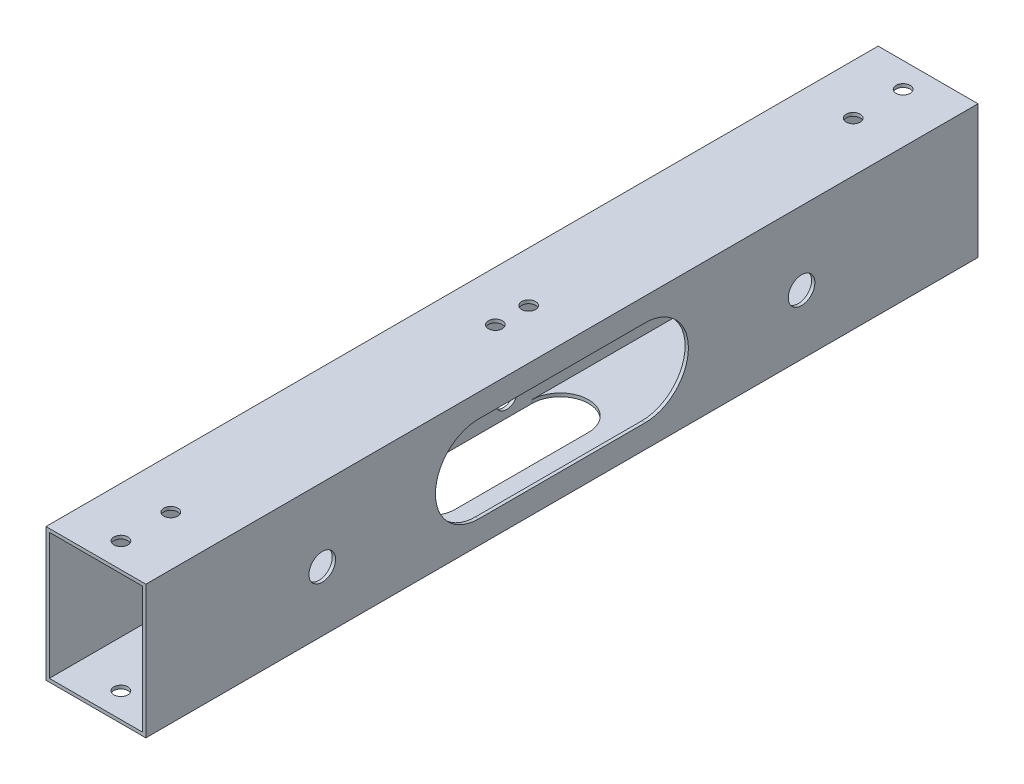
SolidWorks part; units mm, degrees
material "6061 合金"
ref_plane "前视基准面" through (0, 0, 0) normal (0, 0, 1) x (1, 0, 0)
ref_plane "上视基准面" through (0, 0, 0) normal (0, 1, 0) x (1, 0, 0)
ref_plane "右视基准面" through (0, 0, 0) normal (1, 0, 0) x (0, 0, -1)
other "Configuration Table"
sketch "草图1" plane through (0, 0, 0) normal (0, 0, 1) x (1, 0, 0)
  line L0 (15, -20) -> (15, 20)
  line L1 (15, 20) -> (-15, 20)
  line L2 (-15, 20) -> (-15, -20)
  line L3 (-15, -20) -> (15, -20)
  line L4 (14, 19) -> (-14, 19)
  line L5 (14, -19) -> (14, 19)
  line L6 (-14, -19) -> (14, -19)
  line L7 (-14, 19) -> (-14, -19)
extrude "凸台-拉伸1" add sketch "草图1" along normal blind 250
sketch "草图3" plane through (0, 20, 0) normal (0, 1, 0) x (1, 0, 0)
  line L0 (15, 0) -> (-15, 0) construction
  line L1 (0, 0) -> (0, -44.5469) construction
  line L2 (-15, -125) -> (78.6025, -125) construction
  line L4 (-15, -250) -> (-15, 0) construction
  circle A0 centre (0, -7.5) radius 2.1
  circle A1 centre (0, -22.5) radius 2.1
  circle A4 centre (0, -227.5) radius 2.1
  circle A5 centre (0, -242.5) radius 2.1
  circle A6 centre (0, -120) radius 2.1
  circle A7 centre (0, -130) radius 2.1
  dimension "D1" = 4.2
  dimension "D2" = 7.5
  dimension "D4" = 0
  dimension "D5" = 4.2
  dimension "D6" = 10
  dimension "D3" = 2
extrude "切除-拉伸1" cut sketch "草图3" against normal blind 250
sketch "草图4" plane through (15, 0, 0) normal (1, 0, 0) x (0, 0, -1)
  line L0 (-250, 20) -> (0, 20) construction
  line L1 (0, -20) -> (0, 20) construction
  line L2 (-125, 20) -> (-125, -104.7599) construction
  circle A0 centre (-53, -2) radius 4
  circle A1 centre (-197, -2) radius 4
  dimension "D1" = 8
  dimension "D2" = 22
  dimension "D3" = 53
extrude "切除-拉伸2" cut sketch "草图4" against normal blind 250
sketch "草图5" plane through (-15, 0, 0) normal (-1, 0, 0) x (0, 0, 1)
  line L0 (250, 20) -> (0, 20) construction
  circle A0 centre (125, -2) radius 7
  dimension "D1" = 22
  dimension "D2" = 14
extrude "切除-拉伸3" cut sketch "草图5" against normal blind 250
sketch "草图6" plane through (0, -20, 0) normal (0, -1, 0) x (1, 0, 0)
  line L0 (-15, 250) -> (-15, 0) construction
  line L2 (-14, 145) -> (-14, 105)
  line L4 (3, 145) -> (3, 105)
  line L5 (-15, 125) -> (57.9688, 125) construction
  line L6 (15, 250) -> (15, 0) construction
  arc A0 (3, 145) -> (-14, 145) centre (-5.5, 145) ccw
  arc A1 (-14, 105) -> (3, 105) centre (-5.5, 105) ccw
  dimension "D4" = 20
  dimension "D5" = 8.5
  dimension "D7" = 20.5
  dimension "D8" = 8.5
  dimension "D1" = 17
  dimension "D2" = 1
  dimension "D3" = 40
  dimension "D6" = 12
extrude "切除-拉伸4" cut sketch "草图6" against normal blind 20
sketch "草图7" plane through (15, 0, 0) normal (1, 0, 0) x (0, 0, -1)
  line L0 (-125, 20) -> (-125, -74.6216) construction
  line L1 (-250, 20) -> (0, 20) construction
  line L2 (-150, 0) -> (-100, 0) construction
  line L3 (-150, 13) -> (-100, 13)
  line L4 (-150, -13) -> (-100, -13)
  arc A0 (-150, 13) -> (-150, -13) centre (-150, 0) ccw
  arc A1 (-100, -13) -> (-100, 13) centre (-100, 0) ccw
  point P8 (-125, 0)
  dimension "D2" = 25
  dimension "D3" = 13
  dimension "D1" = 50
extrude "切除-拉伸6" cut sketch "草图7" against normal blind 22
sketch "草图8" plane through (-15, 0, 0) normal (-1, 0, 0) x (0, 0, 1)
  line L0 (125, 20) -> (125, -55.4072) construction
  line L1 (250, 20) -> (0, 20) construction
  line L2 (250, -20) -> (0, -20) construction
  circle A0 centre (112.625, -14.5) radius 3.25
  circle A1 centre (137.375, -14.5) radius 3.25
  circle A2 centre (112.625, 10.25) radius 3.25
  circle A3 centre (137.375, 10.25) radius 3.25
  dimension "D1" = 24.75
  dimension "D2" = 5.5
  dimension "D4" = 24.75
  dimension "D5" = 6.5
  dimension "D3" = 2
extrude "切除-拉伸7" cut sketch "草图8" against normal blind 22
